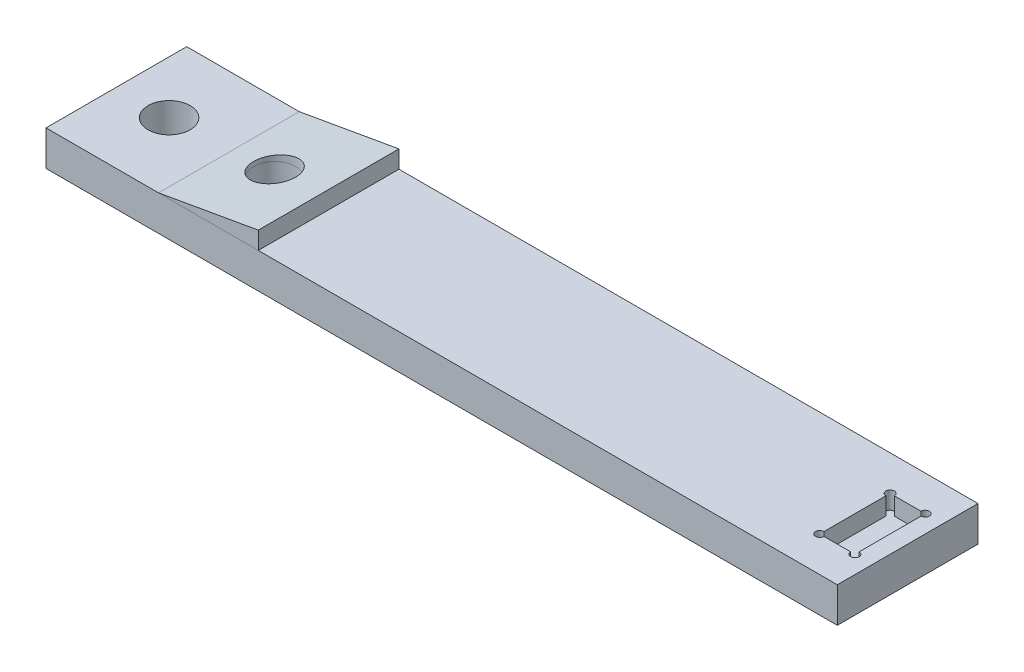
SolidWorks part; units mm, degrees
material "6061 Alloy"
ref_plane "Front Plane" through (0, 0, 0) normal (0, 0, 1) x (1, 0, 0)
ref_plane "Top Plane" through (0, 0, 0) normal (0, 1, 0) x (1, 0, 0)
ref_plane "Right Plane" through (0, 0, 0) normal (1, 0, 0) x (0, 0, -1)
sketch "Sketch1" plane through (0, 0, 0) normal (0, 1, 0) x (1, 0, 0)
  line L1 (-35.7187, -6.35) -> (35.7188, -6.35)
  line L2 (-35.7187, -6.35) -> (-35.7187, 6.35)
  line L3 (-35.7187, 6.35) -> (35.7188, 6.35)
  line L4 (35.7188, -6.35) -> (35.7188, 6.35)
  line L5 (-35.7187, -6.35) -> (35.7188, 6.35) construction
  line L6 (-35.7187, 6.35) -> (35.7188, -6.35) construction
  point P0 (0, 0)
  dimension "D1" = 12.7
  dimension "D2" = 71.4375
extrude "Boss-Extrude1" add sketch "Sketch1" along normal blind 3.175
sketch "Sketch2" plane through (0, 0, 6.35) normal (0, 0, 1) x (1, 0, 0)
  line L0 (-25.5587, 3.175) -> (-16.5556, 4.7625)
  line L1 (-35.7187, 3.175) -> (35.7188, 3.175) construction
  line L2 (-16.5556, 4.7625) -> (-16.5556, 3.175)
  line L3 (-16.5556, 3.175) -> (-25.5587, 3.175)
  dimension "D1" = 10.16
  dimension "D2" = 1.5875
  dimension "D3" = 80
extrude "Boss-Extrude2" add sketch "Sketch2" against normal blind 12.7 separate body
sketch "Sketch3" plane through (0, 3.175, 0) normal (0, 1, 0) x (1, 0, 0)
  line L0 (35.7188, 6.35) -> (-35.7187, 6.35) construction
  line L1 (30.9563, -3.175) -> (34.1313, -3.175)
  line L2 (30.9563, -3.175) -> (30.9563, 3.175)
  line L3 (30.9563, 3.175) -> (34.1313, 3.175)
  line L4 (34.1313, -3.175) -> (34.1313, 3.175)
  line L5 (30.9563, -3.175) -> (34.1313, 3.175) construction
  line L6 (30.9563, 3.175) -> (34.1313, -3.175) construction
  line L7 (35.7188, -6.35) -> (35.7188, 6.35) construction
  circle A0 centre (34.1313, -3.175) radius 0.381
  circle A1 centre (34.1313, 3.175) radius 0.381
  circle A2 centre (30.9563, 3.175) radius 0.381
  circle A3 centre (30.9563, -3.175) radius 0.381
  point P0 (32.5438, 0)
  dimension "D5" = 0.762
  dimension "D6" = 0.762
  dimension "D7" = 0.762
  dimension "D8" = 0.762
  dimension "D1" = 6.35
  dimension "D2" = 3.175
  dimension "D3" = 3.175
  dimension "D4" = 1.5875
extrude "Cut-Extrude1" cut sketch "Sketch3" against normal blind 1.5875 contours A3 L1 A0 L4 A1 L3 A2 L2 | L3 A2 L2 | L2 A2 L3 | L2 A3 L1 | L1 A3 L2 | L1 A0 L4 | L4 A0 L1 | L3 A1 L4 | L4 A1 L3 | L4 L3 L2 L1 region at (31.118, 3.175, 3.0133) region at (30.9023, 3.175, 3.2289) region at (32.5438, 3.175, 0) region at (33.9695, 3.175, 3.0133) region at (34.1852, 3.175, 3.2289) region at (30.9023, 3.175, -3.2289) region at (31.118, 3.175, -3.0133) region at (33.9695, 3.175, -3.0133) region at (34.1852, 3.175, -3.2289)
hole_wizard "#6 Clearance Hole2" positions "Sketch4" profile "Sketch5" hole size "#6" standard "ANSI Inch" end condition through all
sketch "Sketch4" plane through (0, 0, 0) normal (0, -1, 0) x (-1, 0, 0)
  line L0 (35.7187, 6.35) -> (35.7187, -6.35) construction
  line L1 (-35.7188, 6.35) -> (35.7187, 6.35) construction
  point P0 (30.9562, 0)
  point P2 (21.4312, 0)
  dimension "D1" = 4.7625
  dimension "D2" = 9.525
  dimension "D3" = 6.35
  dimension "D4" = 6.35
sketch "Sketch5" plane through (-30.9562, 0, 0) normal (1, 0, 0) x (0, 0, -1)
  line L0 (0, 0) -> (0, 4.7625)
  line L1 (0, 4.7625) -> (1.8986, 4.7625)
  line L2 (1.8986, 4.7625) -> (1.8986, 0)
  line L5 (1.8986, 0) -> (0, 0)
  line L11 (0, -6.35) -> (0, 107.95) construction
  dimension "Thru Hole Dia." = 3.7973
  dimension "Thru Hole Depth" = 4.7625
